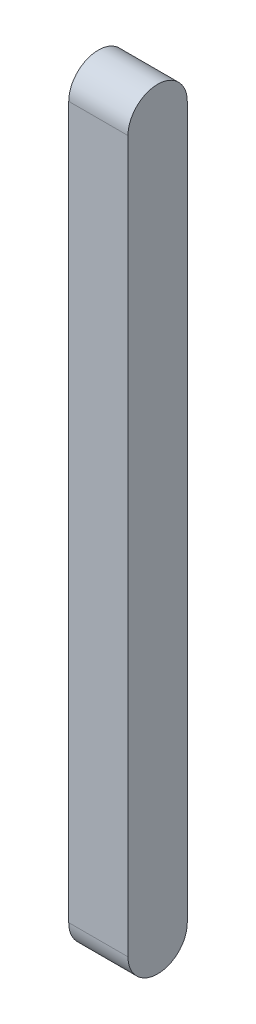
SolidWorks part; units mm, degrees
ref_plane "前视基准面" through (0, 0, 0) normal (0, 0, 1) x (1, 0, 0)
ref_plane "上视基准面" through (0, 0, 0) normal (0, 1, 0) x (1, 0, 0)
ref_plane "右视基准面" through (0, 0, 0) normal (1, 0, 0) x (0, 0, -1)
sketch "草图1" plane through (0, 0, 0) normal (1, 0, 0) x (0, 0, -1)
  line L1 (-5, 60) -> (5, 60)
  line L2 (-5, 60) -> (-5, -60)
  line L3 (-5, -60) -> (5, -60)
  line L4 (5, 60) -> (5, -60)
  line L5 (-5, 60) -> (5, -60) construction
  line L6 (-5, -60) -> (5, 60) construction
  circle A0 centre (0, 60) radius 5
  circle A1 centre (0, -60) radius 5
  point P0 (0, 0)
extrude "凸台-拉伸1" add sketch "草图1" along normal blind 10 contours L3 A1 | A0 | A1 | L2 L3 L4 L1 region at (0, -62.1221, 0)
